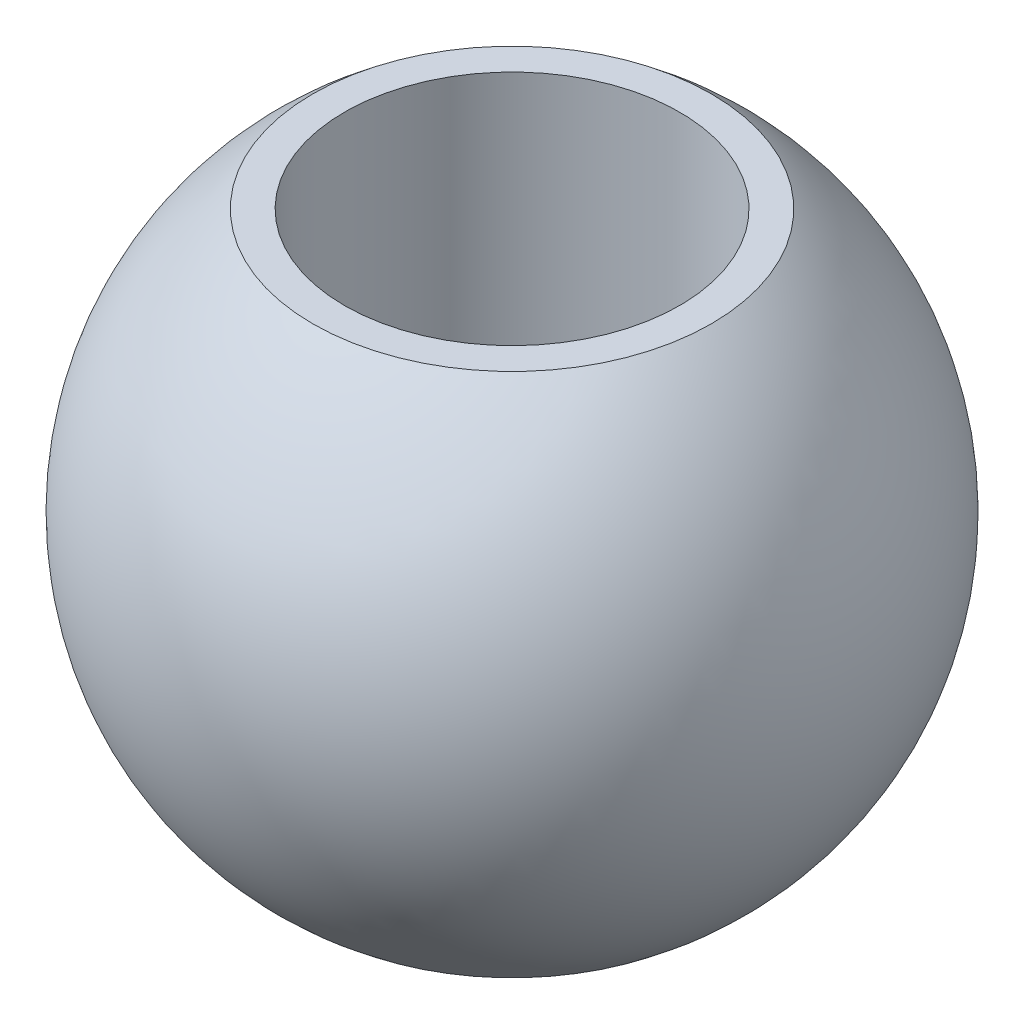
SolidWorks part; units mm, degrees
ref_plane "Front Plane" through (0, 0, 0) normal (0, 0, 1) x (1, 0, 0)
ref_plane "Top Plane" through (0, 0, 0) normal (0, 1, 0) x (1, 0, 0)
ref_plane "Right Plane" through (0, 0, 0) normal (1, 0, 0) x (0, 0, -1)
sketch "Sketch2" plane through (0, 0, 0) normal (0, 0, 1) x (1, 0, 0)
  line L0 (0, 2.35) -> (0, -2.35)
  line L1 (0, 2.35) -> (1.7833, 2.35)
  line L2 (0, 0) -> (2.95, 0) construction
  line L3 (0, -2.35) -> (1.7833, -2.35)
  arc A0 (1.7833, -2.35) -> (1.7833, 2.35) centre (0, 0) ccw
  dimension "D1" = 2.95
  dimension "D2" = 4.7
revolve "Revolve1" add sketch "Sketch2" angle 360 about L0
sketch "Sketch3" plane through (0, 2.35, 0) normal (0, 1, 0) x (1, 0, 0)
  circle A0 centre (0, 0) radius 1.5
  dimension "D1" = 3
extrude "Cut-Extrude1" cut sketch "Sketch3" against normal up to surface (4.7 mm away) up to face at (0, -2.35, 1.7833)
